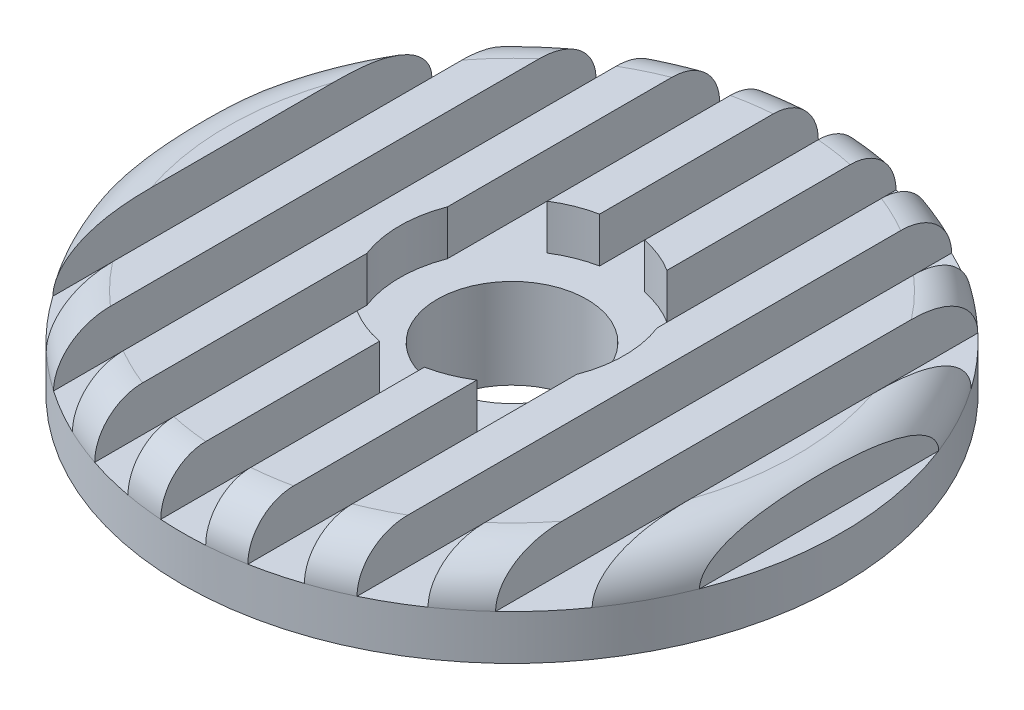
SolidWorks part; units mm, degrees
ref_plane "Front Plane" through (0, 0, 0) normal (0, 0, 1) x (1, 0, 0)
ref_plane "Top Plane" through (0, 0, 0) normal (0, 1, 0) x (1, 0, 0)
ref_plane "Right Plane" through (0, 0, 0) normal (1, 0, 0) x (0, 0, -1)
sketch "Sketch1" plane through (0, 0, 0) normal (0, 1, 0) x (1, 0, 0)
  circle A0 centre (0, 0) radius 22
  circle A1 centre (0, 0) radius 10
  circle A2 centre (0, 0) radius 5
  circle A3 centre (0, 0) radius 7.5
  dimension "D1" = 44
  dimension "D2" = 20
  dimension "D3" = 10
  dimension "D4" = 15
extrude "Boss-Extrude2" add sketch "Sketch1" along normal mid plane 6 contours A0 A1 | A1 A3 | A3 A2 region at (-21.3777, 0, 0) region at (-9.7172, 0, 0) region at (-7.2879, 0, 0)
fillet "Fillet2" radius 3 1 edges at (0, 3, 22)
extrude "Cut-Extrude3" cut sketch "Sketch1<5>" along normal through all contours A3
sketch "Sketch1<5>" plane through (0, 0, 0) normal (0, 1, 0) x (1, 0, 0) same geometry as "Sketch1"
extrude "Boss-Extrude3" add sketch "Sketch1<9>" against normal blind 3 from surface contours A1 | A2 starting at face at (0, -3, 22)
sketch "Sketch1<9>" plane through (0, 0, 0) normal (0, 1, 0) x (1, 0, 0) same geometry as "Sketch1"
sketch "Sketch2" plane through (0, 0, 0) normal (0, 1, 0) x (1, 0, 0)
  line L0 (-4.95, 0) -> (4.95, 0) construction
  line L1 (-20.5, 25) -> (-23.5, 25)
  line L2 (-20.5, 25) -> (-20.5, -25)
  line L3 (-20.5, -25) -> (-23.5, -25)
  line L4 (-23.5, 25) -> (-23.5, -25)
  line L5 (-20.5, 25) -> (-23.5, -25) construction
  line L6 (-20.5, -25) -> (-23.5, 25) construction
  line L7 (0, -4.95) -> (0, 4.95) construction
  point P0 (-22, 0)
  dimension "D1" = 50
  dimension "D2" = 3
  dimension "D3" = 20.5
extrude "Cut-Extrude4" cut sketch "Sketch2" along normal through all
sketch "Sketch4" plane through (0, 0, 0) normal (0, 1, 0) x (1, 0, 0)
  line L0 (-25.8899, 0) -> (27.7335, 0) construction
  line L1 (-4.95, 0) -> (4.95, 0) construction
pattern_linear "LPattern1" count 9 spacing 5.5 along (1, 0, 0) of "Cut-Extrude4"
